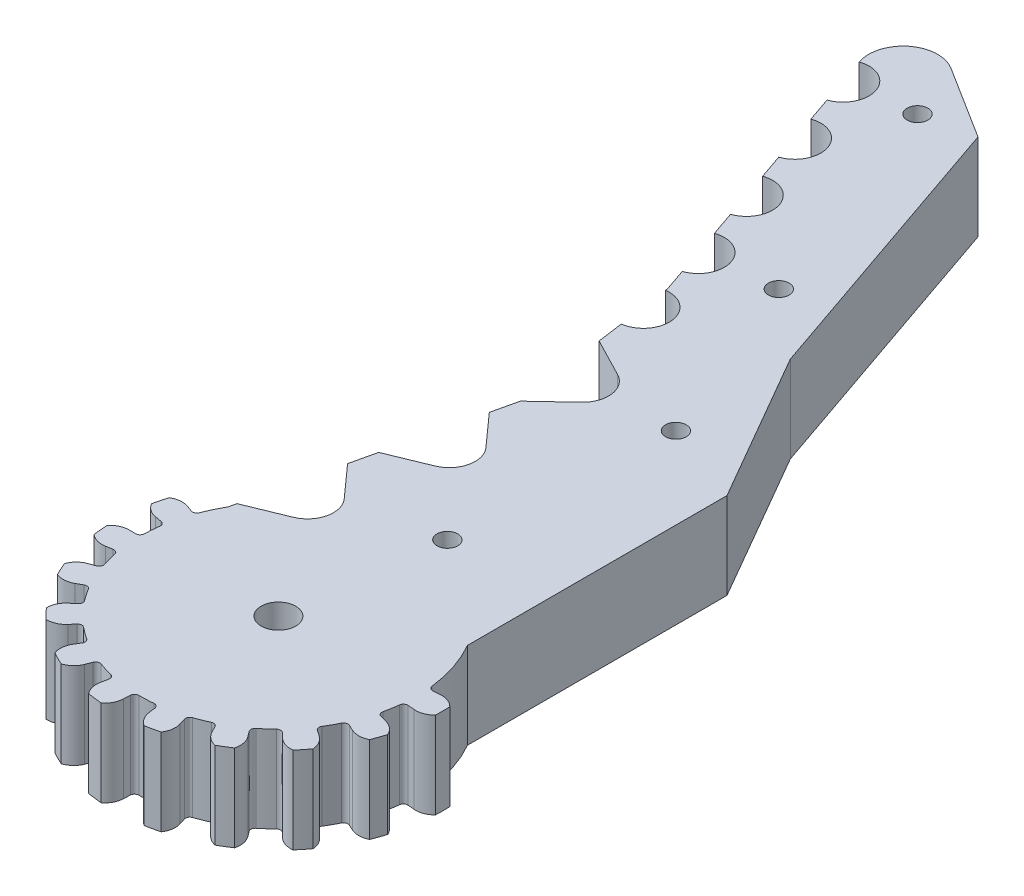
SolidWorks part; units mm, degrees
material "1060 Alloy"
ref_plane "Front" through (0, 0, 0) normal (0, 0, 1) x (1, 0, 0)
ref_plane "Top" through (0, 0, 0) normal (0, 1, 0) x (1, 0, 0)
ref_plane "Right" through (0, 0, 0) normal (1, 0, 0) x (0, 0, -1)
sketch "Sketch1" plane through (0, 0, 0) normal (0, 1, 0) x (1, 0, 0)
  line L0 (-16, 0) -> (16, 0) construction
  line L1 (0, 16) -> (0, -16) construction
  line L2 (0, 0) -> (-13.8564, 8) construction
  line L3 (-13.8564, 8) -> (-13.8564, 38) construction
  line L4 (-13.8564, 38) -> (-3.8564, 55.3205) construction
  line L5 (-3.8564, 55.3205) -> (7.5385, 88.4137) construction
  line L6 (7.5385, 88.4137) -> (16, 93.7431) construction
  line L7 (21.9138, 89.0562) -> (10.2977, 55.3205) construction
  line L8 (10.2977, 55.3205) -> (7.5385, 35.5118) construction
  line L9 (7.5385, 35.5118) -> (13.8564, 8) construction
  line L10 (0, 0) -> (13.8564, 8) construction
  line L11 (0, 0) -> (86.4562, 0) construction
  line L12 (86.4562, -39.4101) -> (86.4562, 112.6901) construction
  line L13 (172.9124, 0) -> (159.056, 8) construction
  line L14 (172.9124, 0) -> (186.7688, 8) construction
  line L15 (172.9124, 16) -> (172.9124, -16) construction
  line L16 (188.9124, 0) -> (156.9124, 0) construction
  line L17 (165.3739, 35.5118) -> (159.056, 8)
  line L18 (162.6147, 55.3205) -> (165.3739, 35.5118)
  line L19 (150.9986, 89.0562) -> (162.6147, 55.3205)
  line L20 (165.3739, 88.4137) -> (156.9124, 93.7431)
  line L21 (176.7688, 55.3205) -> (165.3739, 88.4137)
  line L22 (186.7688, 38) -> (176.7688, 55.3205)
  line L23 (186.7688, 8) -> (186.7688, 38)
  circle A0 centre (0, 0) radius 16 construction
  arc A1 (16, 93.7431) -> (21.9138, 89.0562) centre (18.1318, 90.3585) cw construction
  arc A2 (156.9124, 93.7431) -> (150.9986, 89.0562) centre (154.7806, 90.3585) ccw
  circle A3 centre (172.9124, 0) radius 16
  dimension "D1" = 32
  dimension "D8" = 4
  dimension "D2" = 30
  dimension "D3" = 20
  dimension "D4" = 35
  dimension "D5" = 10
  dimension "D6" = 60
  dimension "D7" = 71
  dimension "D9" = 30
  dimension "D10" = 86.4562
extrude "Boss-Extrude1" add sketch "Sketch1" along normal blind 10 contours L17 A3 L23 L22 L21 L20 A2 L19 L18 | A3 region at (170.1634, 0, -47.9725) region at (172.9124, 0, 0)
sketch "Sketch2" plane through (0, 10, 0) normal (0, 1, 0) x (1, 0, 0)
  line L0 (165.3739, 35.5118) -> (159.056, 8) construction
  line L1 (162.6147, 55.3205) -> (165.3739, 35.5118) construction
  line L2 (150.9986, 89.0562) -> (162.6147, 55.3205) construction
  line L3 (165.3739, 35.5118) -> (159.056, 8)
  line L4 (162.6147, 55.3205) -> (165.3739, 35.5118)
  line L5 (150.9986, 89.0562) -> (162.6147, 55.3205)
  line L6 (163.9014, 46.0832) -> (168.3426, 43.7863)
  line L7 (165.3739, 35.5118) -> (169.0183, 38.9349)
  line L8 (164.7025, 32.5879) -> (168.0372, 28.8624)
  line L9 (162.3143, 22.1886) -> (166.9403, 24.0859)
  line L10 (161.6429, 19.2647) -> (164.9776, 15.5392)
  line L11 (159.2547, 8.8654) -> (163.8807, 10.7627)
  arc A0 (150.9986, 89.0562) -> (152.952, 83.3831) centre (151.9753, 86.2196) cw
  arc A1 (153.9287, 80.5465) -> (155.8821, 74.8734) centre (154.9054, 77.71) cw
  arc A2 (156.8588, 72.0369) -> (158.8122, 66.3637) centre (157.8355, 69.2003) cw
  arc A3 (159.7889, 63.5272) -> (161.7423, 57.8541) centre (160.7656, 60.6906) cw
  arc A4 (162.6597, 54.9972) -> (163.4875, 49.0545) centre (163.0736, 52.0259) cw
  arc A5 (168.3426, 43.7863) -> (169.0183, 38.9349) centre (166.9644, 41.1216) cw
  arc A6 (168.0372, 28.8624) -> (166.9403, 24.0859) centre (165.8019, 26.8615) cw
  arc A7 (164.9776, 15.5392) -> (163.8807, 10.7627) centre (162.7423, 13.5383) cw
  line M17 (150.9986, 89.0562) -> (162.6147, 55.3205)
  dimension "D1" = 3
  dimension "D2" = 9
  dimension "D8" = 3
  dimension "D3" = 18
  dimension "D4" = 27
  dimension "D5" = 36
  dimension "D6" = 3
  dimension "D7" = 5
  dimension "D9" = 3
  dimension "D10" = 10.67
  dimension "D11" = 3
  dimension "D12" = 10.67
extrude "Cut-Extrude1" cut sketch "Sketch2" against normal blind 10 contours A0 M17 | A1 M17 | A2 M17 | A3 M17 | A4 L4 | A5 L6 L4 L7 | A6 L8 L3 L9 | A7 L10 L3 L11 region at (162.5238, 10, -13.5885) region at (165.5834, 10, -26.9117) region at (153.1791, 10, -86.6342) region at (156.1092, 10, -78.1245) region at (159.0394, 10, -69.6148) region at (161.9695, 10, -61.1052) region at (164.3347, 10, -52.2015) region at (166.7445, 10, -41.091)
sketch "Sketch3" plane through (0, 10, 0) normal (0, 1, 0) x (1, 0, 0)
  line L0 (172.9124, 0) -> (203.9745, 0) construction
  line L1 (172.9124, 0) -> (203.9234, 1.354) construction
  line L2 (188.8515, 1.3945) -> (190.0968, 1.5034)
  line L3 (172.9124, 0) -> (203.8896, 2.7102) construction
  line L4 (188.8515, -1.3945) -> (190.0968, -1.5034)
  arc A0 (159.056, 8) -> (186.7688, 8) centre (172.9124, 0) ccw construction
  arc A1 (159.056, 8) -> (186.7688, 8) centre (172.9124, 0) ccw
  circle A2 centre (172.9124, 0) radius 17.25 construction
  circle A3 centre (172.9124, 0) radius 19 construction
  arc A4 (190.0968, 1.5034) -> (191.8943, 0.8288) centre (190.2906, -0.7121) cw
  arc A5 (191.8943, -0.8288) -> (191.8943, 0.8288) centre (172.9124, 0) ccw
  arc A6 (190.0968, -1.5034) -> (191.8943, -0.8288) centre (190.2906, 0.7121) ccw
  arc M31 (159.056, 8) -> (186.7688, 8) centre (172.9124, 0) ccw
  dimension "D1" = 1.25
  dimension "D2" = 3
  dimension "D3" = 2.5
  dimension "D4" = 5
extrude "Boss-Extrude2" add sketch "Sketch3" against normal up to surface (10 mm away) contours L4 A6 A5 A4 L2 M31 region at (190.3245, 10, 0) up to face at (164.3499, 0, -46.4477)
fillet "Fillet1" radius 0.5 2 edges at (188.8515, 5, -1.3945) (188.8515, 5, 1.3945)
pattern_circular "CirPattern1" count 19 over 350 about axis through (172.9124, 10, 0) along (0, -1, 0) skipping 11, 12, 13, 14, 15, 16, 17, 18 of "Fillet1", "Boss-Extrude2"
ref_axis "Axis1" through (172.9124, 0, 0) along (0, 1, 0)
sketch "Sketch4" plane through (0, 10, 0) normal (0, 1, 0) x (1, 0, 0)
  line L0 (188.9124, 0) -> (156.9124, 0) construction
  circle A0 centre (172.9124, 0) radius 2
  dimension "D1" = 4
extrude "Cut-Extrude2" cut sketch "Sketch4" against normal through all contours A0
sketch "Sketch5" plane through (0, 10, 0) normal (0, 1, 0) x (1, 0, 0)
  line L0 (154.8118, 87.1963) -> (165.7931, 87.1963) construction
  line L1 (176.7688, 55.3205) -> (165.3739, 88.4137) construction
  line L2 (163.6022, 61.6673) -> (174.5834, 61.6673) construction
  line L3 (163.3102, 17.4019) -> (186.7688, 17.4019) construction
  line L4 (161.6429, 19.2647) -> (164.9776, 15.5392) construction
  line L5 (186.7688, 8) -> (186.7688, 38) construction
  line L6 (169.9357, 41.5355) -> (184.7276, 41.5355) construction
  line L7 (186.7688, 38) -> (176.7688, 55.3205) construction
  line L8 (159.5931, 87.1963) -> (159.5931, 92.0547) construction
  line L9 (165.3739, 88.4137) -> (156.9124, 93.7431) construction
  arc A0 (152.952, 83.3831) -> (150.9986, 89.0562) centre (151.9753, 86.2196) ccw construction
  arc A1 (161.7423, 57.8541) -> (159.7889, 63.5272) centre (160.7656, 60.6906) ccw construction
  arc A2 (169.0183, 38.9349) -> (168.3426, 43.7863) centre (166.9644, 41.1216) ccw construction
  circle A3 centre (169.0928, 61.6673) radius 1.2
  circle A4 centre (177.3317, 41.5355) radius 1.2
  circle A5 centre (175.0395, 17.4019) radius 1.2
  circle A6 centre (159.5931, 87.1963) radius 1.2
  dimension "D1" = 2.4
  dimension "D2" = 6.2
extrude "Cut-Extrude3" cut sketch "Sketch5" against normal through all contours A6 | A3 | A4 | A5
